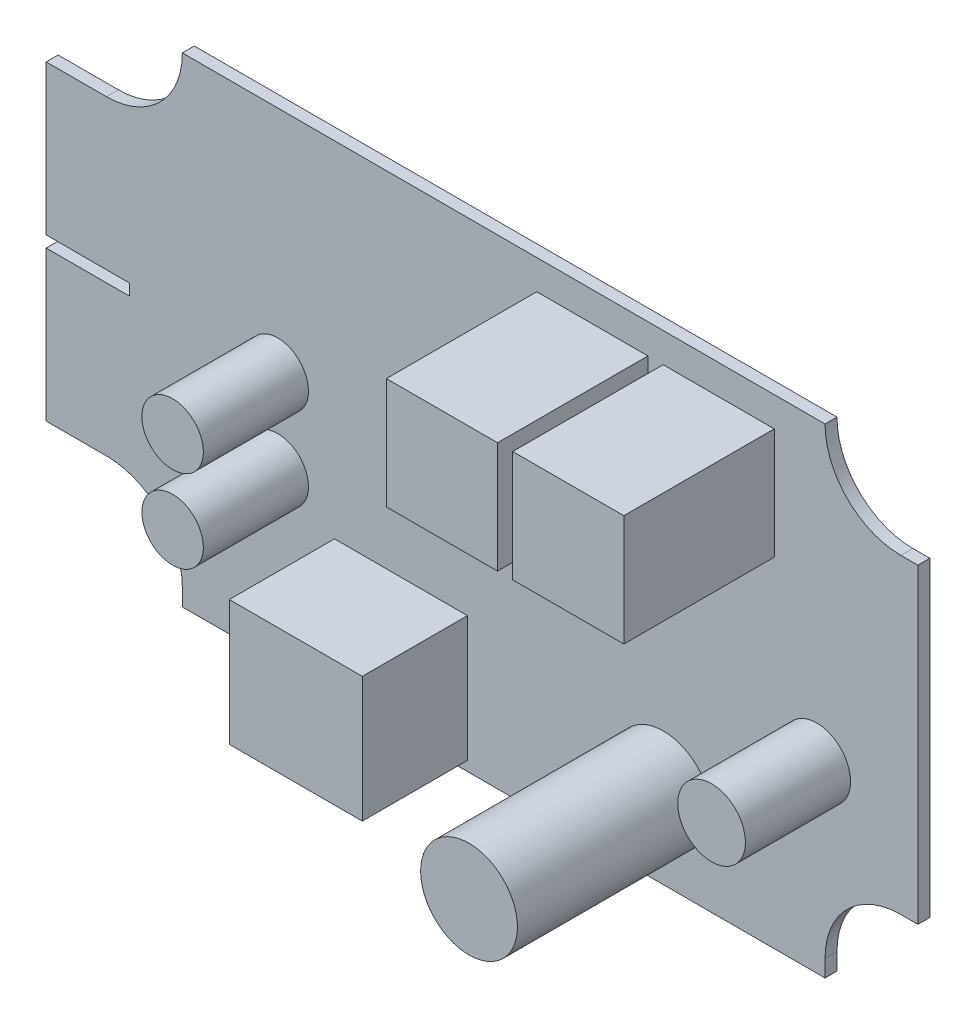
SolidWorks part; units mm, degrees
ref_plane "Front Plane" through (0, 0, 0) normal (0, 0, 1) x (1, 0, 0)
ref_plane "Top Plane" through (0, 0, 0) normal (0, 1, 0) x (1, 0, 0)
ref_plane "Right Plane" through (0, 0, 0) normal (1, 0, 0) x (0, 0, -1)
sketch "Sketch1" plane through (0, 0, 0) normal (0, 0, 1) x (1, 0, 0)
  line L0 (-42.3541, 30.2967) -> (-52.3541, 30.2967) construction
  line L1 (42.3541, -30.7033) -> (42.3541, -32.9433)
  line L2 (-52.3541, -20.7033) -> (-60.3013, -20.7033)
  line L3 (-42.3541, 30.2967) -> (42.3541, 30.2967)
  line L4 (52.3541, -20.7033) -> (54.5933, -20.7033)
  line L5 (-52.3541, 30.2967) -> (-52.3541, 20.2967) construction
  line L6 (-52.3541, -20.7033) -> (-52.3541, -30.7033) construction
  line L7 (-52.3541, -30.7033) -> (-42.3541, -30.7033) construction
  line L8 (42.3541, -30.7033) -> (52.3541, -30.7033) construction
  line L9 (52.3541, -30.7033) -> (52.3541, -20.7033) construction
  line L10 (52.3541, 20.2967) -> (52.3541, 30.2967) construction
  line L11 (52.3541, 30.2967) -> (42.3541, 30.2967) construction
  line L12 (54.5933, -20.7033) -> (54.5933, 20.2967)
  line L13 (-60.3013, -20.7033) -> (-60.3013, -0.9533)
  line L14 (-60.3013, 20.2967) -> (-52.3541, 20.2967)
  line L15 (54.5933, 20.2967) -> (52.3541, 20.2967)
  line L16 (42.3541, -32.9433) -> (-42.3541, -32.9433)
  line L17 (-42.3541, -32.9433) -> (-42.3541, -30.7033)
  line L18 (-60.3013, 0.5467) -> (-49.3013, 0.5467)
  line L19 (-49.3013, 0.5467) -> (-49.3013, -0.9533)
  line L20 (-49.3013, -0.9533) -> (-60.3013, -0.9533)
  line L21 (0, -32.9433) -> (0, 0) construction
  line L22 (-60.3013, 0.5467) -> (-60.3013, 20.2967)
  arc A0 (-42.3541, 30.2967) -> (-52.3541, 20.2967) centre (-52.3541, 30.2967) cw
  arc A2 (-52.3541, -20.7033) -> (-42.3541, -30.7033) centre (-52.3541, -30.7033) cw
  arc A4 (42.3541, 30.2967) -> (52.3541, 20.2967) centre (52.3541, 30.2967) ccw
  arc A5 (52.3541, -20.7033) -> (42.3541, -30.7033) centre (52.3541, -30.7033) ccw
  dimension "D1" = 41
  dimension "D2" = 11
  dimension "D3" = 10
  dimension "D4" = 1.5
  dimension "D6" = 2.24
  dimension "D8" = 2.2392
extrude "Boss-Extrude1" add sketch "Sketch1" along normal blind 1.5748
sketch "Sketch2" plane through (0, 0, 1.5748) normal (0, 0, 1) x (1, 0, 0)
  line L1 (4.3619, 26.3914) -> (19.0119, 26.3914)
  line L2 (4.3619, 26.3914) -> (4.3619, 11.7414)
  line L3 (4.3619, 11.7414) -> (19.0119, 11.7414)
  line L4 (19.0119, 26.3914) -> (19.0119, 11.7414)
  line L5 (21.0119, 26.3914) -> (35.6619, 26.3914)
  line L6 (21.0119, 26.3914) -> (21.0119, 11.7414)
  line L7 (21.0119, 11.7414) -> (35.6619, 11.7414)
  line L8 (35.6619, 26.3914) -> (35.6619, 11.7414)
  dimension "D1" = 2
  dimension "D2" = 14.65
extrude "Boss-Extrude2" add sketch "Sketch2" along normal blind 19.82
sketch "Sketch3" plane through (0, 0, 1.5748) normal (0, 0, 1) x (1, 0, 0)
  circle A0 centre (21.0509, -21.7791) radius 6.38
  dimension "D1" = 12.76
extrude "Boss-Extrude3" add sketch "Sketch3" along normal blind 25.62
sketch "Sketch4" plane through (0, 0, 1.5748) normal (0, 0, 1) x (1, 0, 0)
  line L1 (-22.3027, -15.1438) -> (-4.7739, -15.1438)
  line L2 (-22.3027, -15.1438) -> (-22.3027, -31.671)
  line L3 (-22.3027, -31.671) -> (-4.7739, -31.671)
  line L4 (-4.7739, -15.1438) -> (-4.7739, -31.671)
  circle A0 centre (-29.7754, 0) radius 4.05
  circle A1 centre (-29.7754, -10.91) radius 4.05
  circle A2 centre (41.2613, -8.8411) radius 4.4585
  dimension "D1" = 8.1
  dimension "D2" = 16.5272
  dimension "D4" = 8.9169
  dimension "D3" = 17.5288
extrude "Boss-Extrude4" add sketch "Sketch4" along normal blind 13.86
